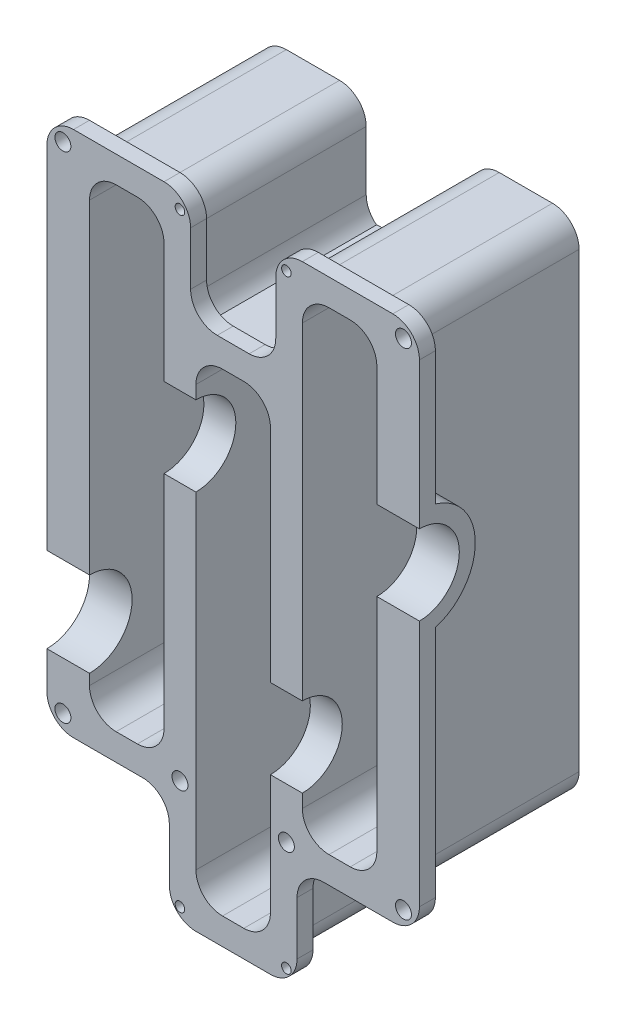
SolidWorks part; units mm, degrees
material "Cast Alloy Steel"
ref_plane "Front Plane" through (0, 0, 0) normal (0, 0, 1) x (1, 0, 0)
ref_plane "Top Plane" through (0, 0, 0) normal (0, 1, 0) x (1, 0, 0)
ref_plane "Right Plane" through (0, 0, 0) normal (1, 0, 0) x (0, 0, -1)
sketch "Sketch1" plane through (0, 0, 0) normal (0, 0, 1) x (1, 0, 0)
  line L1 (-35, -59.5) -> (35, -59.5)
  line L2 (-35, -59.5) -> (-35, 59.5)
  line L3 (-35, 59.5) -> (35, 59.5)
  line L4 (35, -59.5) -> (35, 59.5)
  line L5 (-35, -59.5) -> (35, 59.5) construction
  line L6 (-35, 59.5) -> (35, -59.5) construction
  point P0 (0, 0)
  dimension "D1" = 70
  dimension "D2" = 119
extrude "Boss-Extrude1" add sketch "Sketch1" along normal blind 35
sketch "Sketch2" plane through (-35, 0, 0) normal (-1, 0, 0) x (0, 0, 1)
  line L0 (35, 59.5) -> (35, -59.5) construction
  line L1 (35, -59.5) -> (0, -59.5) construction
  circle A0 centre (35, -19.5) radius 8
  dimension "D1" = 16
  dimension "D2" = 40
extrude "Cut-Extrude1" cut sketch "Sketch2" against normal blind 8
sketch "Sketch3" plane through (0, 0, 35) normal (0, 0, 1) x (1, 0, 0)
  line L0 (-35, 59.5) -> (-35, -11.5) construction
  line L1 (-27, 54.5) -> (-13, 54.5)
  line L2 (-27, 54.5) -> (-27, -34.5)
  line L3 (-27, -34.5) -> (-13, -34.5)
  line L4 (-13, 54.5) -> (-13, 27)
  line L5 (-7, 34.5) -> (7, 34.5)
  line L6 (-7, 34.5) -> (-7, 27)
  line L7 (-7, -54.5) -> (7, -54.5)
  line L8 (7, 34.5) -> (7, -12)
  line L9 (13, 54.5) -> (27, 54.5)
  line L10 (13, 54.5) -> (13, -12)
  line L11 (13, -34.5) -> (27, -34.5)
  line L12 (27, 54.5) -> (27, -34.5)
  line L13 (-35, -19.5) -> (35, -19.5) construction
  line L14 (-35, -11.5) -> (-35, -27.5) construction
  line L15 (35, -59.5) -> (35, 59.5) construction
  line L16 (-35, 19.5) -> (35, 19.5) construction
  line L17 (-13, 27) -> (-7, 27)
  line L18 (-13, 12) -> (-7, 12)
  line L19 (-13, 12) -> (-13, -34.5)
  line L20 (-7, 12) -> (-7, -54.5)
  line L21 (7, -12) -> (13, -12)
  line L22 (7, -27) -> (13, -27)
  line L23 (7, -27) -> (7, -54.5)
  line L24 (13, -27) -> (13, -34.5)
  dimension "D1" = 8
  dimension "D2" = 6
  dimension "D3" = 6
  dimension "D4" = 14
  dimension "D5" = 15
  dimension "D6" = 89
  dimension "D7" = 15
  dimension "D8" = 39
  dimension "D9" = 15
  dimension "D10" = 7.5
  dimension "D11" = 7.5
  dimension "D12" = 89
extrude "Cut-Extrude2" cut sketch "Sketch3" against normal blind 32
sketch "Sketch4" plane through (35, 0, 0) normal (1, 0, 0) x (0, 0, -1)
  line L0 (-35, -59.5) -> (-35, 59.5) construction
  line L1 (-35, -59.5) -> (0, -59.5) construction
  circle A0 centre (-35, 19.5) radius 7.5
  dimension "D1" = 15
  dimension "D2" = 79
extrude "Cut-Extrude3" cut sketch "Sketch4" against normal blind 8
sketch "Sketch5" plane through (0, 0, 35) normal (0, 0, 1) x (1, 0, 0)
  line L0 (35, 59.5) -> (-35, 59.5) construction
  line L1 (-8, 59.5) -> (8, 59.5)
  line L2 (-8, 59.5) -> (-8, 39.5)
  line L3 (-8, 39.5) -> (8, 39.5)
  line L4 (8, 59.5) -> (8, 39.5)
  line L5 (-35, -27.5) -> (-35, -59.5) construction
  line L6 (12, -39.5) -> (35, -39.5)
  line L7 (12, -39.5) -> (12, -59.5)
  line L8 (12, -59.5) -> (35, -59.5)
  line L9 (35, -39.5) -> (35, -59.5)
  line L10 (-35, -39.5) -> (-12, -39.5)
  line L11 (-35, -39.5) -> (-35, -59.5)
  line L12 (-35, -59.5) -> (-12, -59.5)
  line L13 (-12, -39.5) -> (-12, -59.5)
  line L14 (-35, -59.5) -> (35, -59.5) construction
  line L15 (7, -54.5) -> (7, -27) construction
  line L16 (13, -34.5) -> (27, -34.5) construction
  line L17 (-7, 12) -> (-7, -54.5) construction
  line L18 (-27, -34.5) -> (-13, -34.5) construction
  line L19 (13, 54.5) -> (13, -12) construction
  line L20 (-13, 27) -> (-13, 54.5) construction
  line L21 (7, 34.5) -> (-7, 34.5) construction
  dimension "D1" = 5
  dimension "D2" = 5
  dimension "D3" = 5
  dimension "D4" = 5
  dimension "D5" = 5
  dimension "D6" = 5
  dimension "D7" = 5
extrude "Cut-Extrude4" cut sketch "Sketch5" against normal through all
sketch "Sketch6" plane through (35, 0, 0) normal (1, 0, 0) x (0, 0, -1)
  line L9 (-32, 59.5) -> (0, 59.5)
  line L10 (0, 59.5) -> (0, -39.5)
  line L11 (-32, -39.5) -> (-32, 9.4377)
  line L12 (-32, 29.5623) -> (-32, 59.5)
  line L13 (-32, -39.5) -> (-32, 9.4377)
  line L14 (-32, 29.5623) -> (-32, 59.5)
  line L15 (0, -39.5) -> (-32, -39.5)
  arc A4 (-32, 9.4377) -> (-32, 29.5623) centre (-35, 19.5) ccw
  arc A5 (-32, 9.4377) -> (-32, 29.5623) centre (-35, 19.5) ccw
  dimension "D1" = 3
extrude "Cut-Extrude5" cut sketch "Sketch6" against normal blind 5
sketch "Sketch7" plane through (0, -39.5, 0) normal (0, -1, 0) x (1, 0, 0)
  line L1 (30, 32) -> (12, 32)
  line L2 (30, 32) -> (30, 0)
  line L3 (30, 0) -> (12, 0)
  line L4 (12, 32) -> (12, 0)
extrude "Cut-Extrude6" cut sketch "Sketch7" against normal blind 2
sketch "Sketch8" plane through (12, 0, 0) normal (1, 0, 0) x (0, 0, -1)
  line L0 (-32, -37.5) -> (0, -37.5) construction
  line L1 (-32, -37.5) -> (0, -37.5)
  line L2 (-32, -37.5) -> (-32, -59.5)
  line L3 (-32, -59.5) -> (0, -59.5)
  line L4 (0, -37.5) -> (0, -59.5)
  line L5 (-32, -37.5) -> (-32, -39.5) construction
extrude "Cut-Extrude7" cut sketch "Sketch8" against normal blind 2
sketch "Sketch9" plane through (0, -59.5, 0) normal (0, -1, 0) x (1, 0, 0)
  line L1 (10, 32) -> (-12, 32)
  line L2 (10, 32) -> (10, 0)
  line L3 (10, 0) -> (-12, 0)
  line L4 (-12, 32) -> (-12, 0)
extrude "Cut-Extrude8" cut sketch "Sketch9" against normal blind 2
sketch "Sketch10" plane through (-12, 0, 0) normal (-1, 0, 0) x (0, 0, 1)
  line L1 (32, -57.5) -> (0, -57.5)
  line L2 (32, -57.5) -> (32, -39.5)
  line L3 (32, -39.5) -> (0, -39.5)
  line L4 (0, -57.5) -> (0, -39.5)
extrude "Cut-Extrude9" cut sketch "Sketch10" against normal blind 2
sketch "Sketch11" plane through (0, -39.5, 0) normal (0, -1, 0) x (1, 0, 0)
  line L0 (-35, 32) -> (-10, 32)
  line L3 (-12, 0) -> (-35, 0)
  line L4 (-35, 32) -> (-35, 0)
  line L5 (-10, 32) -> (-10, 0)
  line L6 (-10, 0) -> (-12, 0)
sketch "Sketch12" plane through (-35, 0, 0) normal (-1, 0, 0) x (0, 0, 1)
  line L4 (32, 59.5) -> (0, 59.5)
  line L5 (0, 59.5) -> (0, -39.5)
  line L6 (32, -30.083) -> (32, -39.5)
  line L7 (32, 59.5) -> (32, -8.917)
  line L8 (32, -30.083) -> (32, -39.5)
  line L9 (32, 59.5) -> (32, -8.917)
  line L10 (0, -39.5) -> (32, -39.5)
  arc A3 (32, -8.917) -> (32, -30.083) centre (35, -19.5) ccw
  arc A4 (32, -8.917) -> (32, -30.083) centre (35, -19.5) ccw
  dimension "D1" = 3
extrude "Cut-Extrude11" cut sketch "Sketch12" against normal blind 5
sketch "Sketch13" plane through (0, -39.5, 0) normal (0, -1, 0) x (1, 0, 0)
  line L1 (-10, 32) -> (-30, 32)
  line L2 (-10, 32) -> (-10, 0)
  line L3 (-10, 0) -> (-30, 0)
  line L4 (-30, 32) -> (-30, 0)
extrude "Cut-Extrude12" cut sketch "Sketch13" against normal blind 2
sketch "Sketch14" plane through (0, 59.5, 0) normal (0, 1, 0) x (1, 0, 0)
  line L0 (-8, 0) -> (-8, -35) construction
  line L1 (8, 0) -> (30, 0)
  line L2 (8, 0) -> (8, -32)
  line L3 (8, -32) -> (30, -32)
  line L4 (30, 0) -> (30, -32)
  line L5 (-30, 0) -> (-8, 0)
  line L6 (-30, 0) -> (-30, -32)
  line L7 (-30, -32) -> (-8, -32)
  line L8 (-8, 0) -> (-8, -32)
extrude "Cut-Extrude13" cut sketch "Sketch14" against normal blind 2
sketch "Sketch15" plane through (8, 0, 0) normal (-1, 0, 0) x (0, 0, 1)
  line L1 (32, 57.5) -> (0, 57.5)
  line L2 (32, 57.5) -> (32, 39.5)
  line L3 (32, 39.5) -> (0, 39.5)
  line L4 (0, 57.5) -> (0, 39.5)
extrude "Cut-Extrude14" cut sketch "Sketch15" against normal blind 2
sketch "Sketch16" plane through (0, 39.5, 0) normal (0, 1, 0) x (1, 0, 0)
  line L1 (-8, 0) -> (10, 0)
  line L2 (-8, 0) -> (-8, -32)
  line L3 (-8, -32) -> (10, -32)
  line L4 (10, 0) -> (10, -32)
extrude "Cut-Extrude15" cut sketch "Sketch16" against normal blind 2
sketch "Sketch17" plane through (-8, 0, 0) normal (1, 0, 0) x (0, 0, -1)
  line L0 (-32, 57.5) -> (-32, 29.5623) construction
  line L1 (-32, 37.3947) -> (0, 37.3947)
  line L2 (-32, 37.3947) -> (-32, 57.5)
  line L3 (-32, 57.5) -> (0, 57.5)
  line L4 (0, 37.3947) -> (0, 57.5)
extrude "Cut-Extrude16" cut sketch "Sketch17" against normal blind 2
fillet "Fillet1" radius 5 12 edges at (27, -34.5, 19) (13, -34.5, 19) (7, -54.5, 19) (-7, -54.5, 19) (-13, -34.5, 19) (-27, -34.5, 19) (-13, 54.5, 19) (7, 34.5, 19) (27, 54.5, 19) (13, 54.5, 19) (-7, 34.5, 19) (-27, 54.5, 19)
fillet "Fillet3" radius 5 12 edges at (-10, 57.5, 16) (-30, 57.5, 16) (-30, -37.5, 16) (-10, -37.5, 16) (-10, -57.5, 16) (10, -37.5, 16) (30, -37.5, 16) (30, 57.5, 16) (10, 57.5, 16) (10, 37.5, 16) (-10, 37.3947, 16) (10, -57.5, 16)
fillet "Fillet4" radius 5 12 edges at (35, 59.5, 33.5) (8, 59.5, 33.5) (8, 39.5, 33.5) (-8, 39.5, 33.5) (-8, 59.5, 33.5) (-35, 59.5, 33.5) (35, -39.5, 33.5) (12, -39.5, 33.5) (12, -59.5, 33.5) (-12, -59.5, 33.5) (-12, -39.5, 33.5) (-35, -39.5, 33.5)
sketch "Sketch18" plane through (0, 0, 35) normal (0, 0, 1) x (1, 0, 0)
  line L0 (-13, 59.5) -> (-30, 59.5) construction
  line L1 (-32, 56.5) -> (32, 56.5) construction
  line L2 (-32, 56.5) -> (-32, -36.5) construction
  line L3 (-32, -36.5) -> (32, -36.5) construction
  line L4 (32, 56.5) -> (32, -36.5) construction
  line L5 (-35, 54.5) -> (-35, -11.5) construction
  line L6 (-7, 12) -> (-7, -49.5) construction
  line L7 (7, -49.5) -> (7, -27) construction
  circle A0 centre (-32, 56.5) radius 1.5
  circle A1 centre (32, 56.5) radius 1.5
  circle A2 centre (-32, -36.5) radius 1.5
  circle A3 centre (-10, -36.5) radius 1.5
  circle A4 centre (10, -36.5) radius 1.5
  circle A5 centre (32, -36.5) radius 1.5
  dimension "D5" = 3
  dimension "D7" = 3
  dimension "D1" = 64
  dimension "D2" = 93
  dimension "D3" = 3
  dimension "D4" = 3
  dimension "D6" = 3
extrude "Cut-Extrude17" cut sketch "Sketch18" against normal blind 10
sketch "Sketch19" plane through (0, 0, 35) normal (0, 0, 1) x (1, 0, 0)
  line L0 (-8, 54.5) -> (-8, 44.5) construction
  line L1 (-10, 56.5) -> (10, 56.5) construction
  line L2 (-10, 56.5) -> (-10, -57) construction
  line L3 (-10, -57) -> (10, -57) construction
  line L4 (10, 56.5) -> (10, -57) construction
  line L5 (-13, 59.5) -> (-30, 59.5) construction
  circle A0 centre (-10, 56.5) radius 0.9
  circle A1 centre (10, 56.5) radius 0.9
  circle A2 centre (-10, -57) radius 0.9
  circle A3 centre (10, -57) radius 0.9
  dimension "D5" = 1.8
  dimension "D1" = 113.5
  dimension "D2" = 20
  dimension "D3" = 2
  dimension "D4" = 3
extrude "Cut-Extrude18" cut sketch "Sketch19" against normal blind 10
sketch "Sketch20" plane through (13, 0, 0) normal (1, 0, 0) x (0, 0, -1)
  line L0 (-35, -34.5) -> (-35, 12) construction
  line L1 (-35, -12) -> (-3, -12)
  line L2 (-3, -12) -> (-3, -27)
  line L3 (-3, -27) -> (-35, -27)
  arc A1 (-35, -27) -> (-35, -12) centre (-35, -19.5) ccw
  dimension "D1" = 15
extrude "Boss-Extrude3" add sketch "Sketch20" against normal up to surface (6 mm away) up to face at (7, -38.25, 19)
sketch "Sketch21" plane through (-13, 0, 0) normal (-1, 0, 0) x (0, 0, 1)
  line L0 (35, 54.5) -> (35, -11.5) construction
  line L1 (35, 27) -> (3, 27)
  line L2 (3, 27) -> (3, 12)
  line L3 (3, 12) -> (35, 12)
  arc A0 (35, 27) -> (35, 12) centre (35, 19.5) ccw
  dimension "D1" = 15
extrude "Boss-Extrude4" add sketch "Sketch21" against normal up to surface (6 mm away) up to face at (-7, -18.75, 19)
